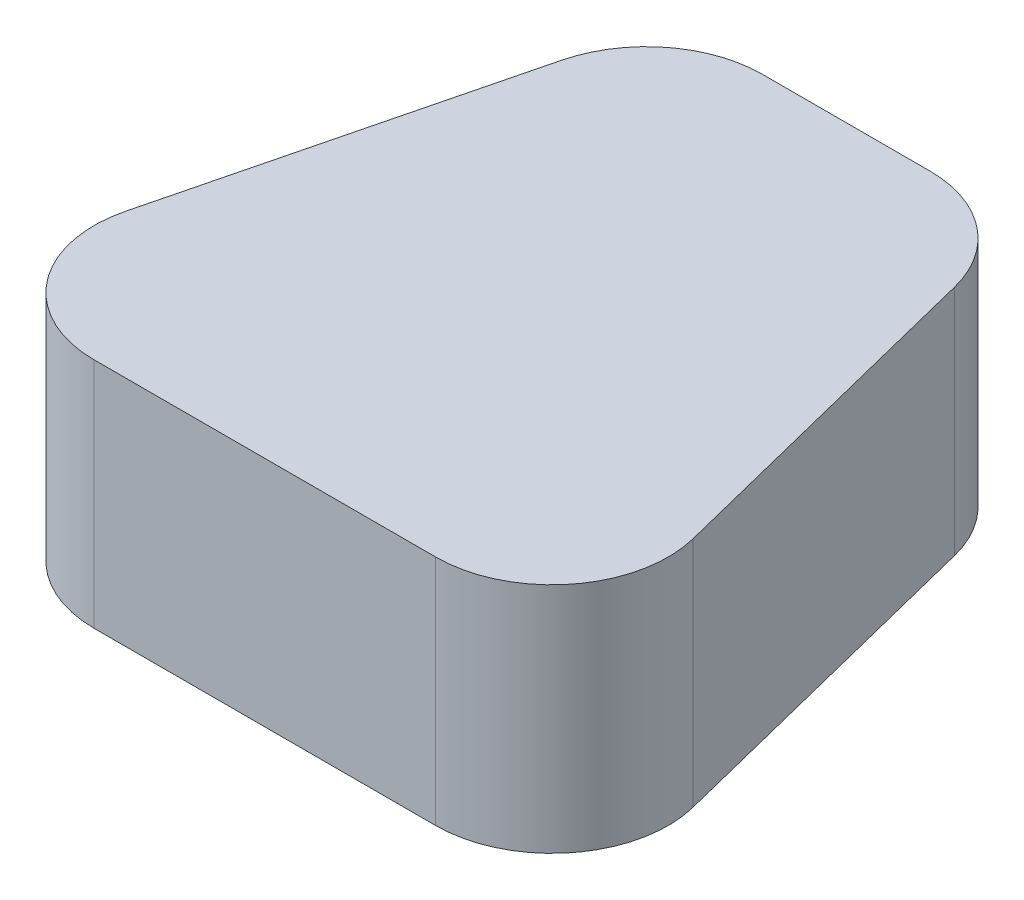
SolidWorks part; units mm, degrees
material "ABS"
ref_plane "前视基准面" through (0, 0, 0) normal (0, 0, 1) x (1, 0, 0)
ref_plane "上视基准面" through (0, 0, 0) normal (0, 1, 0) x (1, 0, 0)
ref_plane "右视基准面" through (0, 0, 0) normal (1, 0, 0) x (0, 0, -1)
ref_plane "ConnectFace" through (0, 0, 0) normal (0, 1, 0) x (1, 0, 0)
ref_plane "CenterV" through (0, 0, 0) normal (1, 0, 0) x (0, 0, -1)
ref_plane "CenterH" through (0, 0, 0) normal (0, 0, 1) x (1, 0, 0)
ref_axis "CenterAxis" through (0, -55, 0) along (0, 1, 0)
sketch "AssemSketch" plane through (0, 0, 0) normal (0, 1, 0) x (1, 0, 0)
  line L0 (0, 25) -> (0, -25) construction
  line L1 (-32.0863, 0) -> (32.0863, 0) construction
  line L2 (0, 0) -> (6.8416, -3.95) construction
  circle A0 centre (0, 0) radius 20
  dimension "H" = 50
  dimension "PinCircle" = 40
  dimension "ang" = 30
  dimension "F" = 7.9
ref_plane "WireConnectFace" through (0, 0, 25) normal (0, 0, 1) x (1, 0, 0)
ref_plane "HeadFace" through (0, 1, 0) normal (0, 1, 0) x (1, 0, 0)
ref_plane "PinCenterH" through (0, 0, 0) normal (-0.5, 0, 0.866) x (0.866, 0, 0.5)
ref_plane "PinCenterV" through (6.8416, 0, 3.95) normal (0.866, 0, 0.5) x (0.5, 0, -0.866)
sketch "SShape1" plane through (0, 1, 0) normal (0, 1, 0) x (1, 0, 0)
  line L0 (0, 25) -> (0, -25) construction
  line L1 (-15, 25) -> (15, 25)
  line L2 (15, 25) -> (27.5, -25)
  line L3 (27.5, -25) -> (-27.5, -25)
  line L4 (-27.5, -25) -> (-15, 25)
  line L5 (-21.25, 0) -> (21.25, 0) construction
  dimension "L1" = 30
  dimension "L2" = 55
  dimension "H" = 50
extrude "FShape1" add sketch "SShape1" along normal blind 20
fillet "FRShape1" radius 10 4 edges at (-15, 11, -25) (15, 11, -25) (27.5, 11, 25) (-27.5, 11, 25)
sketch "SShape2" [suppressed] plane through (0, 1, 0) normal (0, 1, 0) x (1, 0, 0)
  circle A0 centre (0, 0) radius 40
  dimension "D1" = 50
extrude "FShape2" [suppressed] add sketch "SShape2" along normal blind 20
sketch "SPin1aBase" plane through (0, 0, 0) normal (0, 1, 0) x (1, 0, 0)
  circle A1 centre (6.8416, -3.95) radius 5
  circle A2 centre (6.8416, -3.95) radius 5
  dimension "D1" = 0
extrude "FPin1aBase" add sketch "SPin1aBase" along normal up to surface (1 mm away) up to plane "HeadFace"
sketch "SPin1bBase" plane through (0, 0, 0) normal (0, 1, 0) x (1, 0, 0)
  circle A1 centre (-6.8416, -3.95) radius 5
  circle A2 centre (-6.8416, -3.95) radius 5
  dimension "D1" = 0
extrude "FPin1bBase" add sketch "SPin1bBase" along normal up to surface (1 mm away) up to plane "HeadFace"
sketch "SPin2Base" plane through (0, 0, 0) normal (0, 1, 0) x (1, 0, 0)
  circle A1 centre (0, 10.3) radius 5
  circle A2 centre (0, 10.3) radius 5
  dimension "D1" = 0
extrude "FPin2Base" add sketch "SPin2Base" along normal up to surface (1 mm away) up to plane "HeadFace"
equation "\"CtFaceTn\"= 1"
equation "\"H@SShape1\"=\"H@AssemSketch\""
equation "\"D1@SShape2\"=\"H@AssemSketch\""
equation "\"HeadH\"= 20"
equation "\"D1@FShape1\"=\"HeadH\""
equation "\"D1@FShape2\"=\"HeadH\""
